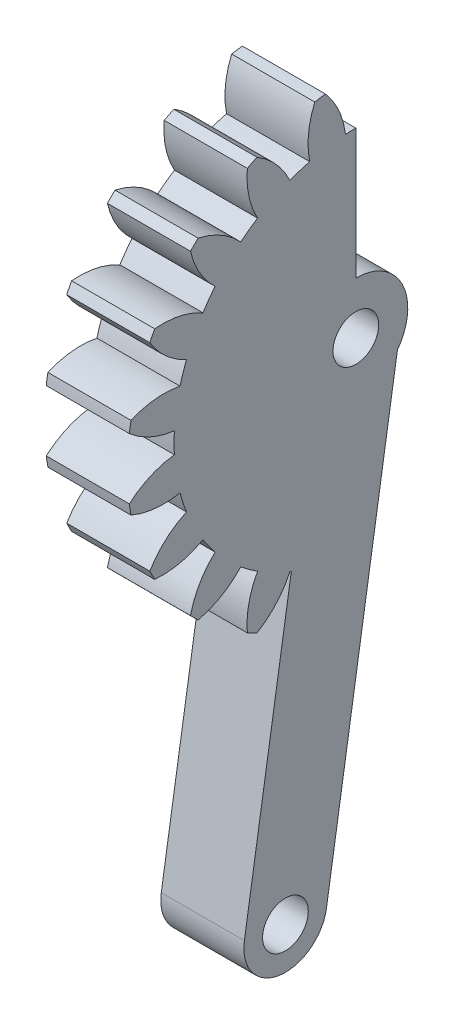
SolidWorks part; units mm, degrees
ref_plane "Plane1" through (0, 0, 0) normal (0, 0, 1) x (1, 0, 0)
ref_plane "Plane2" through (0, 0, 0) normal (0, 1, 0) x (1, 0, 0)
ref_plane "Plane3" through (0, 0, 0) normal (1, 0, 0) x (0, 0, -1)
sketch "HoldingSke" plane through (0, 0, 0) normal (0, 1, 0) x (1, 0, 0)
  line L0 (0, 0) -> (0.9397, -0.342)
  line L1 (-15, 0) -> (100, 0) construction
  line L2 (0, 0) -> (-2.1039, 2.3779)
  line L3 (0, 0) -> (-11.863, 4.5341)
  line L4 (0, 0) -> (8.1152, 2.9537)
  line L5 (0, 0) -> (-46.8476, -17.4728)
  line L6 (0, 0) -> (-1.6579, -1.1186)
  line L7 (-2.1039, 2.3779) -> (8.6586, 51.2059)
  line L8 (-76.2, 54.61) -> (-75.9, 54.61)
  line L9 (-71.009, 38.7566) -> (-53.1078, 45.2721)
  line L10 (-76.2, 71.12) -> (104.1128, 71.12)
  line L11 (0, 0) -> (-2, 0)
  line L12 (-76.2, 101.6) -> (-76.162, 101.6)
  line L13 (24.9733, 27.94) -> (52.9518, 28.4284)
  line L14 (24.9733, 27.94) -> (24.9743, 27.94)
  line L15 (24.9733, 27.94) -> (100.4006, 29.5858)
  line L16 (-63.627, -1) -> (-12.827, -1)
  circle A0 centre (0, 0) radius 1
  circle A1 centre (0, 0) radius 8.749
  circle A2 centre (0, 0) radius 37.5
  circle A3 centre (0, 0) radius 1
  dimension "Num_teeth" = 20
  dimension "Pitch_radius" = 180.3128
  dimension "Width" = 2
sketch "BasProSke" plane through (0, 0, 0) normal (0, 1, 0) x (1, 0, 0)
  line L0 (-10, 0) -> (60, 0) construction
  line L1 (0, 0) -> (0, 11)
  line L2 (0, 0) -> (4, 0)
  line L3 (4, 0) -> (4, 11)
  line L4 (4, 11) -> (0, 11)
  dimension "Thickness" = 4
  dimension "Diameter" = 22
revolve "Base-Revolve" add sketch "BasProSke" angle 360 about L0
sketch "TooCutSke" plane through (0, 0, 0) normal (1, 0, 0) x (0, 0, -1)
  line L1 (0, 0) -> (0, 107) construction
  line L2 (0, 0) -> (-0.8511, 9.9637) construction
  line L3 (0, 0) -> (-3.1206, 19.7028) construction
  line L4 (-0.8511, 9.9637) -> (-1.5603, 9.8514) construction
  arc A0 (0.4999, 8.7347) -> (-0.4999, 8.7347) centre (0, 0) ccw
  arc A1 (1.4852, 10.9249) -> (-1.4852, 10.9249) centre (0, 0) ccw
  circle A2 centre (0, 0) radius 10 construction
  circle A3 centre (0, 0) radius 9.3969 construction
  arc A4 (-0.4999, 8.7347) -> (-1.4852, 10.9249) centre (-4.4722, 8.2645) ccw
  arc A5 (1.4852, 10.9249) -> (0.4999, 8.7347) centre (4.4722, 8.2645) ccw
extrude "ToothCut" cut sketch "TooCutSke" along normal through all
fillet "Breaks" [suppressed] radius 0.02 tangent propagation no
fillet "RootFillets" [suppressed] radius 0.251
pattern_circular "TeethCuts" count 20 every 18 about axis through (-10, 0, 0) along (1, 0, 0) of "ToothCut", "RootFillets", "Breaks"
sketch "HubNeaOneSke" plane through (0, 0, 0) normal (-1, 0, 0) x (0, 0, 1)
  circle A0 centre (0, 0) radius 8.749
  dimension "Diameter" = 17.498
extrude "HubNearOne" [suppressed] add sketch "HubNeaOneSke" along normal blind 46.0001
sketch "HubNeaBotSke" plane through (0, 0, 0) normal (-1, 0, 0) x (0, 0, 1)
  circle A0 centre (0, 0) radius 8.749
  dimension "Diameter" = 17.498
extrude "HubNearBoth" [suppressed] add sketch "HubNeaBotSke" along normal blind 23
ref_plane "FarPln" through (4, 0, 0) normal (1, 0, 0) x (0, 0, -1)
sketch "HubFarSke" plane through (4, 0, 0) normal (1, 0, 0) x (0, 0, -1)
  circle A0 centre (0, 0) radius 8.749
  dimension "Diameter" = 17.498
extrude "HubFar" [suppressed] add sketch "HubFarSke" along normal blind 23
sketch "BorSke" plane through (0, 0, 0) normal (1, 0, 0) x (0, 0, -1)
  circle A0 centre (0, 0) radius 1.1
  dimension "Diameter" = 2.2
extrude "Bore" cut sketch "BorSke" along normal mid plane 100.0001
sketch "KeySke" plane through (0, 0, 0) normal (1, 0, 0) x (0, 0, -1)
  line L0 (-0.4, 0) -> (-0.4, 1.3)
  line L1 (-0.4, 1.3) -> (0.4, 1.3)
  line L2 (0.4, 1.3) -> (0.4, 0)
  line L3 (0, 0) -> (0, 34) construction
  line L4 (-0.4, 0) -> (0.4, 0)
  dimension "Width" = 0.8
extrude "Keyway" [suppressed] cut sketch "KeySke" along normal mid plane 100.0001
pattern_circular "Keyway2" [suppressed] count 2 every 90 about axis through (-10, 0, 0) along (1, 0, 0) reverse direction yes
sketch "草图1" plane through (4, 0, 0) normal (1, 0, 0) x (0, 0, -1)
  line L0 (0, 2.5) -> (0, 12.4015)
  line L1 (0, 12.4015) -> (15.1933, 12.4015)
  line L2 (15.1933, 12.4015) -> (15.1933, -15.03)
  line L3 (15.1933, -15.03) -> (0, -15.03)
  line L4 (0, -15.03) -> (0, -2.5)
  circle A0 centre (0, 0) radius 2.5
  dimension "D1" = 5
extrude "切除-拉伸1" cut sketch "草图1" against normal blind 10 contours A0 L4 L3 L2 L1 L0 region at (4, -1.3459, -7.7543)
sketch "草图5" plane through (0, 0, 0) normal (1, 0, 0) x (0, 0, -1)
  line L0 (0, 0) -> (0, -25)
  line L1 (0, -25) -> (-7.7254, -23.7764)
  line L2 (-7.7254, -23.7764) -> (0, 0)
  line L3 (0, 0) -> (-3.9109, -24.6922)
  line L4 (-7.7736, -24.0804) -> (-0.0481, -25.304)
  point P8 (-3.9109, -24.6922)
  dimension "D1" = 25
  dimension "D2" = 25
  dimension "D3" = 18
  dimension "D4" = 25
ref_plane "基准面1" through (0, -24.6922, 3.9109) normal (0, -0.9877, 0.1564) x (0, -0.1564, -0.9877)
sketch "草图6" plane through (0, -24.6922, 3.9109) normal (0, -0.9877, 0.1564) x (0, -0.1564, -0.9877)
  line L0 (3.9109, 0) -> (-3.9109, 0) construction
  line L1 (-1.7891, 0) -> (2.2109, 0)
  line L2 (-1.7891, 0) -> (-1.7891, 4)
  line L3 (-1.7891, 4) -> (2.2109, 4)
  line L4 (2.2109, 0) -> (2.2109, 4)
  point P4 (-3.9109, 0)
  point P5 (-2.2216, 0)
  point P10 (-0.7344, 4)
  dimension "D1" = 4
  dimension "D2" = 4
  dimension "D3" = 1.7
extrude "凸台-拉伸1" add sketch "草图6" against normal up to next contours L1 L4 L3 L2 region at (2, -24.7252, 3.7026)
fillet "圆角1" radius 2 2 edges at (2, -24.4123, 5.678) (2, -25.0381, 1.7272)
sketch "草图7" plane through (4, 0, 0) normal (1, 0, 0) x (0, 0, -1)
  circle A2 centre (-3.3897, -22.7498) radius 1.1
  arc A3 (-5.3651, -22.4369) -> (-3.7026, -24.7252) centre (-3.3897, -22.7498) ccw construction
  arc A4 (-5.3651, -22.4369) -> (-3.7026, -24.7252) centre (-3.3897, -22.7498) ccw
  dimension "D1" = 2.2
extrude "切除-拉伸2" cut sketch "草图7" against normal blind 10 contours A2 region at (4, -22.7498, 3.3897)
equation "' \"Module@HoldingSke\" = 6.35"
equation "' \"Num_teeth@HoldingSke\" = 12"
equation "' \"Ap@HoldingSke\" =  20"
equation "' \"Ap@HoldingSke\" = 20"
equation "' \"Width@HoldingSke\" = 0.5 * 25.4"
equation "' \"Hub_dia@HoldingSke\"= 1 * 25.4"
equation "' \"Hub_dia@HoldingSke\" = 1 * 25.4"
equation "' \"Overall_len@HoldingSke\" = 1.0 * 25.4"
equation "' \"Bore@HoldingSke\" = 0.75 * 25.4"
equation "' \"T_dim@HoldingSke\" = 0.1 * 25.4"
equation "' \"Width@KeySke\" = 0.25 * 25.4"
equation "' \"Show_teeth@HoldingSke\" = 13"
equation "' \"Backlash@HoldingSke\" = 0.009 * 25.4"
equation "' \"Addendum_fac@HoldingSke\" = 1.0"
equation "' \"Dedendum_fac@HoldingSke\" = 1.25"
equation "' \"Dedendum_add@HoldingSke\" = 0.00005 * 25.4"
equation "' \"Clearance_fac@HoldingSke\" = 0.25"
equation "\"Pitch@HoldingSke\" = 1 / \"Module@HoldingSke\""
equation "\"Overcut_dia@TooCutSke\" = (\"Num_teeth@HoldingSke\" + 2 * \"Addendum_fac@HoldingSke\") / \"Pitch@HoldingSke\" + 0.002 * 25.4"
equation "\"Pitch_dia@TooCutSke\" = \"Num_teeth@HoldingSke\" / \"Pitch@HoldingSke\""
equation "\"Base_dia@TooCutSke\" = \"Num_teeth@HoldingSke\" / \"Pitch@HoldingSke\" * cos((\"Ap@HoldingSke\"  * 3.14159265 / 180))"
equation "\"Root_dia@TooCutSke\" = (\"Num_teeth@HoldingSke\" + 2) / \"Pitch@HoldingSke\" - 2 * (\"Addendum_fac@HoldingSke\" + \"Dedendum_fac@HoldingSke\") / \"Pitch@HoldingSke\" - \"Dedendum_add@HoldingSke\" * 2"
equation "\"Half_ang@TooCutSke\" = 180 / \"Num_teeth@HoldingSke\""
equation "\"Half_CT@TooCutSke\" = \"Num_teeth@HoldingSke\" / \"Pitch@HoldingSke\" * sin((3.14159265 / 2 / \"Num_teeth@HoldingSke\")) / 2 - 7 * \"Backlash@HoldingSke\" / 4"
equation "\"Flank_rad@TooCutSke\" = \"Num_teeth@HoldingSke\" / \"Pitch@HoldingSke\" / 5"
equation "\"Radius@RootFillets\" = \"Clearance_fac@HoldingSke\" / \"Pitch@HoldingSke\" + \"Dedendum_add@HoldingSke\""
equation "\"Break_rad@Breaks\" = 0.02 / \"Pitch@HoldingSke\""
equation "\"Thickness@HoldingSke\" = \"Width@HoldingSke\""
equation "\"OAL@HoldingSke\" = \"Thickness@HoldingSke\""
equation "\"MHD@HoldingSke\" = (\"Num_teeth@HoldingSke\" + 2) / \"Pitch@HoldingSke\" - 2 * (\"Addendum_fac@HoldingSke\" + \"Dedendum_fac@HoldingSke\")  / \"Pitch@HoldingSke\" - \"Dedendum_add@HoldingSke\" * 2"
equation "\"MBD@HoldingSke\" = (\"Num_teeth@HoldingSke\" + 2) / \"Pitch@HoldingSke\" - 2 * (\"Addendum_fac@HoldingSke\" + \"Dedendum_fac@HoldingSke\")  / \"Pitch@HoldingSke\" - \"Dedendum_add@HoldingSke\" * 2 - 0.002 * 25.4"
equation "\"MHD@HoldingSke\" = ((sgn( \"MHD@HoldingSke\" - \"Hub_dia@HoldingSke\" )-1)*( \"MHD@HoldingSke\" - \"Hub_dia@HoldingSke\" ))/-2+ \"Hub_dia@HoldingSke\""
equation "\"MBD@HoldingSke\" = ((sgn( \"MBD@HoldingSke\" - \"Bore@HoldingSke\" )-1)*( \"MBD@HoldingSke\" - \"Bore@HoldingSke\" ))/-2+ \"Bore@HoldingSke\""
equation "\"OAL@HoldingSke\" = ((sgn( \"OAL@HoldingSke\" - \"Overall_len@HoldingSke\" )+1)*( \"OAL@HoldingSke\" - \"Overall_len@HoldingSke\" ))/2 + \"Overall_len@HoldingSke\" + 0.000002 * 25.4"
equation "\"Num_teeth@TeethCuts\" = int( \"Show_teeth@HoldingSke\" ) + 1"
equation "\"Num_teeth@TeethCuts\" = ((sgn( \"Num_teeth@TeethCuts\" - \"Num_teeth@HoldingSke\" )-1)*( \"Num_teeth@TeethCuts\" - \"Num_teeth@HoldingSke\" ))/-2+ \"Num_teeth@HoldingSke\""
equation "\"Num_teeth@TeethCuts\" = ((sgn( \"Num_teeth@TeethCuts\" - 2.0)+1)*( \"Num_teeth@TeethCuts\" - 2.0))/2 +2.0"
equation "\"Angle@TeethCuts\" = 360.0 / \"Num_teeth@HoldingSke\""
equation "\"Diameter@BasProSke\" = (\"Num_teeth@HoldingSke\" + 2 * \"Addendum_fac@HoldingSke\") / \"Pitch@HoldingSke\""
equation "' \"Fillet_rad@BasProSke\" =  \"Thickness@HoldingSke\" * 0.05"
equation "' \"Fillet_rad@BasProSke\" = \"Thickness@HoldingSke\" * 0.05"
equation "\"MHD@HoldingSke\" = ((sgn( \"MHD@HoldingSke\" - \"Root_dia@TooCutSke\" )-1)*( \"MHD@HoldingSke\" - \"Root_dia@TooCutSke\" ))/-2+ \"Root_dia@TooCutSke\""
equation "\"Diameter@HubNeaOneSke\" = \"MHD@HoldingSke\""
equation "\"Length@HubNearOne\" = \"OAL@HoldingSke\" - \"Thickness@BasProSke\""
equation "\"Diameter@HubNeaBotSke\" = \"MHD@HoldingSke\""
equation "\"Length@HubNearBoth\" = ( \"OAL@HoldingSke\" - \"Thickness@BasProSke\" ) / 2.0"
equation "\"Thickness@FarPln\" = \"Thickness@BasProSke\""
equation "\"Diameter@HubFarSke\" = \"MHD@HoldingSke\""
equation "\"Length@HubFar\" = ( \"OAL@HoldingSke\" - \"Thickness@BasProSke\" ) / 2.0"
equation "\"D1@Bore\" = \"OAL@HoldingSke\" * 2.0"
equation "\"D1@Keyway\" = \"OAL@HoldingSke\" * 2.0"
equation "\"Offset@KeySke\" = \"T_dim@HoldingSke\" + \"MBD@HoldingSke\" / 2.0"
